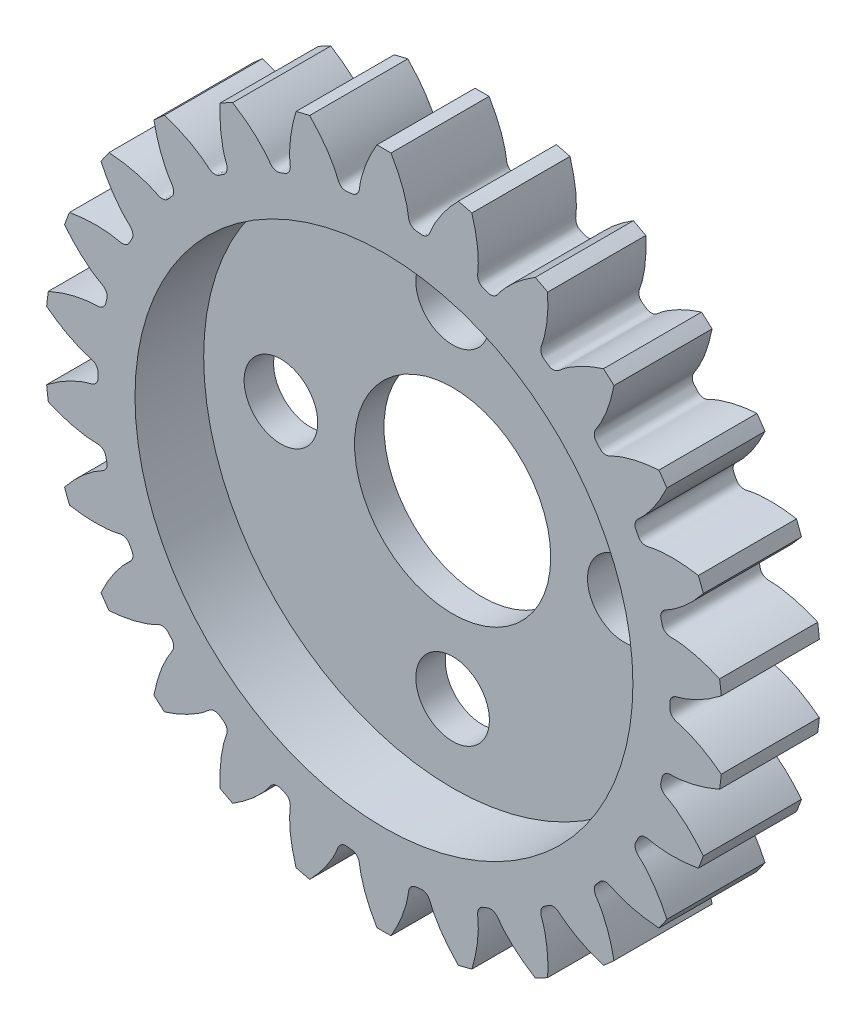
SolidWorks part; units mm, degrees
material "Д16 ГОСТ 4784-97"
ref_plane "FRONT" through (0, 0, 0) normal (0, 0, 1) x (1, 0, 0)
ref_plane "TOP" through (0, 0, 0) normal (0, 1, 0) x (1, 0, 0)
ref_plane "RIGHT" through (0, 0, 0) normal (1, 0, 0) x (0, 0, -1)
ref_axis "Ось1" through (0, 0, 50) along (0, 0, -1)
sketch "SketchRevolveSpurAssemblyNew2Pinion" plane through (0, 0, 0) normal (1, 0, 0) x (0, 0, -1)
  line L0 (0, 0) -> (1, 0) construction
  line L1 (-4, 0) -> (-4, 13.8221)
  line L2 (-4, 13.8221) -> (0, 13.8221)
  line L3 (0, 13.8221) -> (0, 0)
  line L4 (0, 0) -> (-4, 0)
  point P6 (0, 0)
  dimension "D1" = 4
  dimension "D2" = 4
revolve "SpurAssemblyNew2Pinion" add sketch "SketchRevolveSpurAssemblyNew2Pinion" angle 360 about L0
sketch "SketchToothSpurAssemblyNew2Pinion" plane through (0, 0, 0) normal (0, 0, 1) x (1, 0, 0)
  arc A0 (13.8145, 1.4289) -> (13.8145, -1.4289) centre (0, 0) cw
  spline S0 degree 3 poles (13.8145, -1.4289) (13.7267, -1.3599) (13.5952, -1.2613) (13.4189, -1.1388) (13.2926, -1.0553) (13.1699, -0.9783) (13.051, -0.9075) (12.9361, -0.8427) (12.8254, -0.7837) (12.7191, -0.7302) (12.6175, -0.6819) (12.5207, -0.6387) (12.4289, -0.6003) (12.3422, -0.5664) (12.2609, -0.5368) (12.185, -0.5112) (12.1147, -0.4893) (12.0271, -0.4637) (11.9541, -0.4482) (11.8978, -0.428) (11.8759, -0.419) (11.8534, -0.4085) (11.8302, -0.3959) (11.806, -0.3807) (11.7805, -0.3619) (11.7539, -0.3382) (11.7266, -0.3079) (11.7001, -0.2694) (11.6771, -0.2215) (11.6616, -0.1665) (11.6562, -0.0913) (11.6603, 0) (11.6562, 0.0913) (11.6616, 0.1665) (11.6771, 0.2215) (11.7001, 0.2694) (11.7266, 0.3079) (11.7539, 0.3382) (11.7805, 0.3619) (11.806, 0.3807) (11.8302, 0.3959) (11.8534, 0.4085) (11.8759, 0.419) (11.8978, 0.428) (11.9541, 0.4482) (12.0271, 0.4637) (12.1147, 0.4893) (12.185, 0.5112) (12.2609, 0.5368) (12.3422, 0.5664) (12.4289, 0.6003) (12.5207, 0.6387) (12.6175, 0.6819) (12.7191, 0.7302) (12.8254, 0.7837) (12.9361, 0.8427) (13.051, 0.9075) (13.1699, 0.9783) (13.2926, 1.0553) (13.4189, 1.1388) (13.5952, 1.2613) (13.7267, 1.3599) (13.8145, 1.4289) knots 0 0 0 0 0.061766 0.090857 0.118755 0.145459 0.170969 0.195285 0.218406 0.240334 0.261068 0.280608 0.298954 0.316106 0.332064 0.346827 0.360397 0.372773 0.397299 0.401522 0.405868 0.410405 0.415225 0.420444 0.426212 0.432709 0.440141 0.448702 0.45849 0.469388 0.4801 0.5 0.5199 0.530612 0.54151 0.551298 0.559859 0.567291 0.573788 0.579556 0.584775 0.589595 0.594132 0.598478 0.602701 0.627227 0.639603 0.653173 0.667936 0.683894 0.701046 0.719392 0.738932 0.759666 0.781594 0.804715 0.829031 0.854541 0.881245 0.909143 0.938234 1 1 1 1
extrude "ToothExtrudeCutSpurAssemblyNew2Pinion" cut sketch "SketchToothSpurAssemblyNew2Pinion" against normal blind 4 and the other way blind 4
pattern_circular "PatternSpurAssemblyNew2Pinion" count 26 every 13.846 about axis through (0, 0, 50) along (0, 0, -1) of "ToothExtrudeCutSpurAssemblyNew2Pinion"
sketch "AuxiliarySketchSpurAssemblyNew2Pinion" plane through (0, 0, 0) normal (0, 0, 1) x (1, 0, 0)
  circle A0 centre (0, 0) radius 12.5 construction
  circle A1 centre (0, 0) radius 11.7462 construction
  circle A2 centre (0, 0) radius 11.9829 construction
  circle A3 centre (0, 0) radius 13.8221 construction
  circle A4 centre (0, 0) radius 11.6587 construction
  dimension "PitchDiameter" = 25
  dimension "BaseDiameter" = 23.4923
  dimension "FormDiameter" = 23.9658
  dimension "MajorDiameter" = 27.6442
  dimension "MinorDiameter" = 23.3173
sketch "Эскиз2" plane through (0, 0, 4) normal (0, 0, 1) x (1, 0, 0)
  circle A0 centre (0, 0) radius 10.15
extrude "Вырез-Вытянуть2" cut sketch "Эскиз2" against normal blind 2.8
sketch "Эскиз1" plane through (0, 0, 1.2) normal (0, 0, 1) x (1, 0, 0)
  circle A0 centre (0, 0) radius 7 construction
  circle A1 centre (0, 0) radius 8.5 construction
  circle A2 centre (0, 7) radius 1.5
  circle A3 centre (7, 0) radius 1.5
  circle A4 centre (0, -7) radius 1.5
  circle A5 centre (-7, 0) radius 1.5
  circle A6 centre (0, 0) radius 4
extrude "Вырез-Вытянуть1" cut sketch "Эскиз1" against normal through all
